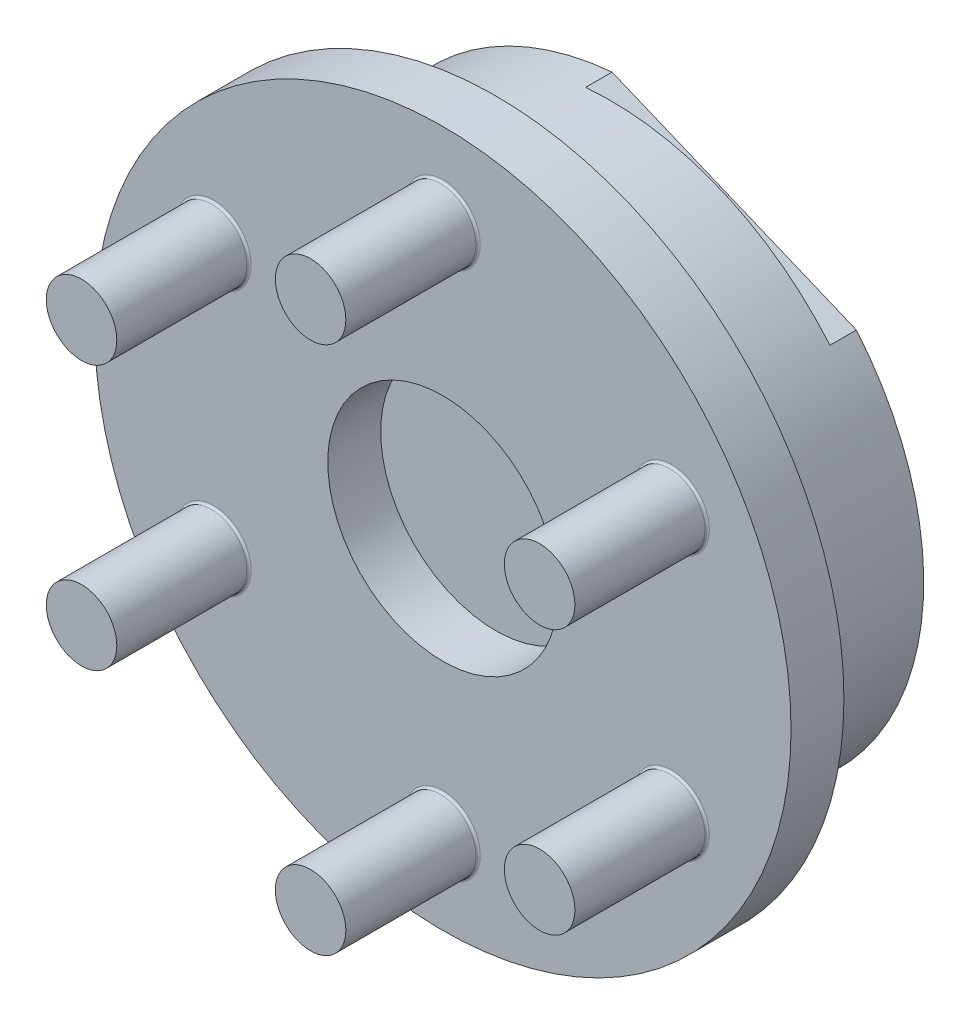
SolidWorks part; units mm, degrees
material "7075-T6, Plate (SS)"
ref_plane "Front Plane" through (0, 0, 0) normal (0, 0, 1) x (1, 0, 0)
ref_plane "Top Plane" through (0, 0, 0) normal (0, 1, 0) x (1, 0, 0)
ref_plane "Right Plane" through (0, 0, 0) normal (1, 0, 0) x (0, 0, -1)
sketch "Sketch1" plane through (0, 0, 0) normal (0, 0, 1) x (1, 0, 0)
  circle A0 centre (0, 0) radius 39.5
  circle A1 centre (0, 30) radius 4
  circle A2 centre (0, 0) radius 13.05
  circle A3 centre (25.9808, 15) radius 4
  circle A4 centre (25.9808, -15) radius 4
  circle A5 centre (0, -30) radius 4
  circle A6 centre (-25.9808, -15) radius 4
  circle A7 centre (-25.9808, 15) radius 4
  point P18 (0, 0)
  dimension "D1" = 79
  dimension "D3" = 8
  dimension "D4" = 26.1
  dimension "D2" = 30
  dimension "D5" = 6
extrude "Boss-Extrude1" add sketch "Sketch1" against normal blind 6 contours A0 | A2
extrude "Boss-Extrude2" add sketch "Sketch1<3>" along normal blind 15 contours A3 | A4 | A5 | A6 | A7 | A1 region at (25.9808, 15, 0) region at (25.9808, -15, 0) region at (0, -30, 0) region at (-25.9808, -15, 0) region at (-25.9808, 15, 0)
sketch "Sketch1<3>" plane through (0, 0, 0) normal (0, 0, 1) x (1, 0, 0) same geometry as "Sketch1"
sketch "Sketch2" plane through (0, 0, -6) normal (0, 0, -1) x (-1, 0, 0)
  circle A0 centre (0, 0) radius 32.55
  circle A1 centre (0, 0) radius 17.5
  circle A4 centre (0, 0) radius 25 construction
  point P18 (0, 0)
  dimension "D1" = 65.1
  dimension "D2" = 50
  dimension "D3" = 35
extrude "Boss-Extrude3" add sketch "Sketch2" along normal blind 16 contours A0
sketch "Sketch3" plane through (0, 0, -22) normal (0, 0, -1) x (-1, 0, 0)
  circle A0 centre (0, 0) radius 25 construction
  point P3 (0, 25)
  point P7 (17.6777, 17.6777)
  point P8 (25, 0)
  point P9 (17.6777, -17.6777)
  point P10 (0, -25)
  point P11 (-17.6777, -17.6777)
  point P12 (-25, 0)
  point P13 (-17.6777, 17.6777)
  point P14 (0, 0)
  point P17 (0, 0)
  dimension "D1" = 50
  dimension "D2" = 8
sketch "Sketch5" plane through (0, 0, 0) normal (0, 0, 1) x (1, 0, 0)
  circle A0 centre (0, 30) radius 4
  circle A1 centre (25.9808, 15) radius 4
  circle A2 centre (25.9808, -15) radius 4
  circle A3 centre (0, -30) radius 4
  circle A4 centre (-25.9808, -15) radius 4
  circle A5 centre (-25.9808, 15) radius 4
  point P15 (0, 0)
  dimension "D2" = 8
  dimension "D1" = 30
  dimension "D3" = 6
extrude "Boss-Extrude4" [suppressed] add sketch "Sketch5" along normal blind 15
fillet "Fillet1" [suppressed] radius 0.5
hole_wizard "M5 Tapped Hole1" positions "Sketch6" profile "Sketch7" tap size "M5" standard "ISO"
sketch "Sketch6" plane through (0, 0, -22) normal (0, 0, -1) x (-1, 0, 0)
  point P0 (0, 25)
  point P3 (-17.6777, 17.6777)
  point P6 (-25, 0)
  point P9 (17.6777, 17.6777)
  point P12 (25, 0)
  point P15 (-17.6777, -17.6777)
  point P18 (0, -25)
  point P21 (17.6777, -17.6777)
sketch "Sketch7" plane through (0, 25, -22) normal (1, 0, 0) x (0, 1, 0)
  line L0 (0, 0) -> (0, 8.2618)
  line L1 (0, 8.2618) -> (2.1, 7)
  line L2 (2.1, 7) -> (2.1, 0.425)
  line L3 (2.1, 0.425) -> (2.525, 0)
  line L5 (2.525, 0) -> (0, 0)
  line L6 (-2.1, 0.425) -> (-2.525, 0) construction
  line L10 (0, 8.2618) -> (-2.1, 7) construction
  line L11 (0, -6.35) -> (0, 107.95) construction
  dimension "Tap Drill Dia." = 4.2
  dimension "Tap Drill Depth" = 7
  dimension "Near C'Sink Dia." = 5.05
  dimension "Near C'Sink Angle" = 90
  dimension "Drill Angle" = 118
sketch "Sketch9" plane through (0, 0, -22) normal (0, 0, -1) x (-1, 0, 0)
  line L0 (0, 0) -> (-12.4563, 30.0723) construction
  line L1 (-24.9131, 20.9486) -> (2.8033, 32.4291)
  line L2 (0, 0) -> (0, 32.55) construction
  line L3 (24.9131, -20.9486) -> (-2.8033, -32.4291)
  circle A0 centre (0, 0) radius 32.55 construction
  arc A1 (2.8033, 32.4291) -> (-24.9131, 20.9486) centre (0, 0) ccw
  circle A2 centre (0, 0) radius 18.5
  arc A3 (-2.8033, -32.4291) -> (24.9131, -20.9486) centre (0, 0) ccw
  point P13 (0, 0)
  dimension "D1" = 37
  dimension "D2" = 22.5
  dimension "D3" = 30
  dimension "D4" = 2
extrude "Cut-Extrude1" cut sketch "Sketch9" against normal blind 13 contours A2
sketch "Sketch10" plane through (0, 0, -22) normal (0, 0, -1) x (-1, 0, 0)
  line L1 (24.9131, -20.9486) -> (-2.8033, -32.4291)
  line L2 (24.9131, -20.9486) -> (-2.8033, -32.4291)
  line L3 (-24.9131, 20.9486) -> (2.8033, 32.4291)
  line L4 (-24.9131, 20.9486) -> (2.8033, 32.4291)
  arc A3 (-2.8033, -32.4291) -> (24.9131, -20.9486) centre (0, 0) ccw
  arc A4 (-2.8033, -32.4291) -> (24.9131, -20.9486) centre (0, 0) ccw
  arc A5 (2.8033, 32.4291) -> (-24.9131, 20.9486) centre (0, 0) ccw
  arc A6 (2.8033, 32.4291) -> (-24.9131, 20.9486) centre (0, 0) ccw
  dimension "D2" = 0
  dimension "D3" = 0
extrude "Cut-Extrude2" cut sketch "Sketch10" against normal blind 3
fillet "Fillet2" radius 0.25 6 edges at (4, -30, 0) (29.9808, -15, 0) (-21.9808, -15, 0) (29.9808, 15, 0) (-21.9808, 15, 0) (4, 30, 0)
